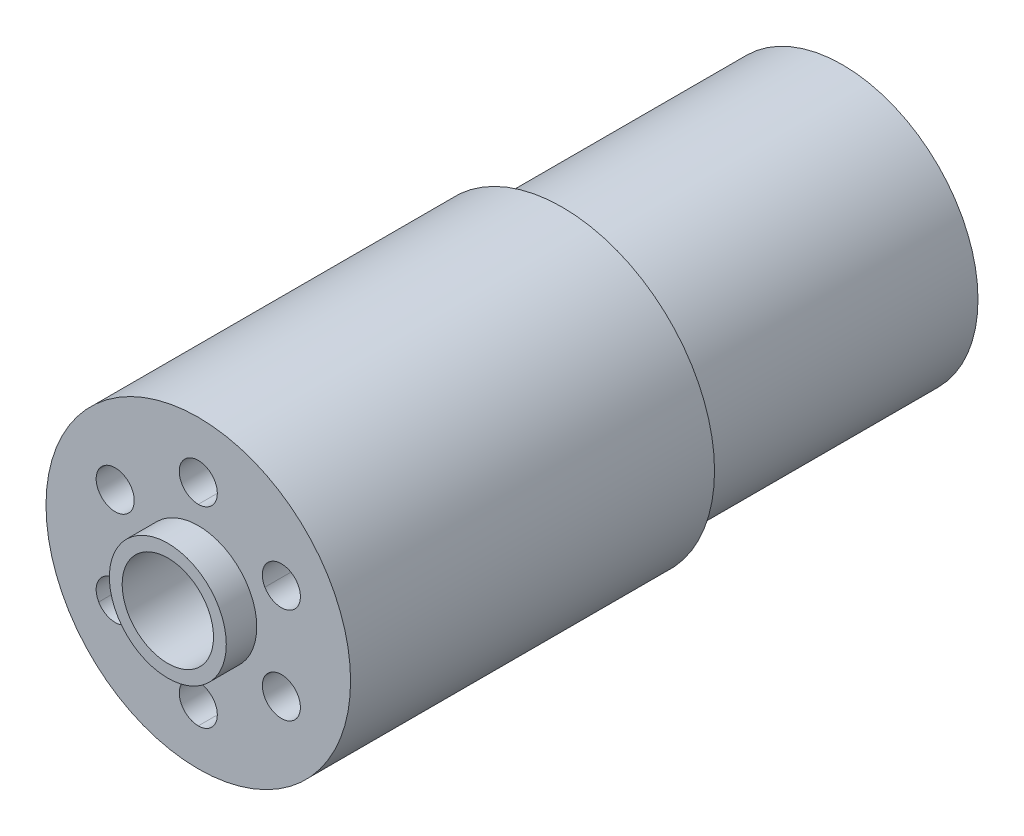
SolidWorks part; units mm, degrees
ref_plane "Front Plane" through (0, 0, 0) normal (0, 0, 1) x (1, 0, 0)
ref_plane "Top Plane" through (0, 0, 0) normal (0, 1, 0) x (1, 0, 0)
ref_plane "Right Plane" through (0, 0, 0) normal (1, 0, 0) x (0, 0, -1)
sketch "Sketch1" plane through (0, 0, 0) normal (0, 0, 1) x (1, 0, 0)
  circle A0 centre (0, 0) radius 25.4
  circle A8 centre (0, 0) radius 9.3953
  point P19 (0, 0)
  dimension "D1" = 50.8
  dimension "D2" = 16.0047
extrude "Boss-Extrude2" add sketch "Sketch1" along normal blind 107.442 contours A0
sketch "Sketch6" plane through (0, 0, 0) normal (0, 0, -1) x (-1, 0, 0)
  circle A0 centre (0, 0) radius 7.62
  circle A1 centre (-13.8581, 8.001) radius 3.175
  circle A2 centre (0, 16.002) radius 3.175
  circle A3 centre (13.8581, 8.001) radius 3.175
  circle A4 centre (13.8581, -8.001) radius 3.175
  circle A5 centre (0, -16.002) radius 3.175
  circle A6 centre (-13.8581, -8.001) radius 3.175
  point P18 (0, 0)
  dimension "D1" = 15.24
  dimension "D2" = 6.35
  dimension "D3" = 16.002
  dimension "D4" = 6
extrude "Cut-Extrude1" cut sketch "Sketch6" against normal blind 108.458
sketch "Sketch7" plane through (0, 0, 0) normal (0, 0, -1) x (-1, 0, 0)
  circle A0 centre (0, 0) radius 22.606
  circle A1 centre (0, 0) radius 25.4 construction
  circle A2 centre (0, 0) radius 25.4
  dimension "D1" = 2.794
extrude "Cut-Extrude2" cut sketch "Sketch7" against normal blind 46.736
sketch "Sketch8" plane through (0, 0, 107.442) normal (0, 0, 1) x (1, 0, 0)
  circle A0 centre (0, 0) radius 7.62
  circle A1 centre (0, 0) radius 9.75
  dimension "D1" = 19.5
  dimension "D2" = 15.24
extrude "Boss-Extrude7" add sketch "Sketch8" along normal blind 5.08
sketch "Sketch9" plane through (0, 0, 0) normal (0, 0, -1) x (-1, 0, 0)
  circle A0 centre (0, 0) radius 7.62
  circle A1 centre (0, 0) radius 9.75
  dimension "D1" = 19.5
  dimension "D2" = 15.24
extrude "Boss-Extrude8" add sketch "Sketch9" along normal blind 5.08
sketch "Sketch10" plane through (0, 0, 0) normal (0, 0, -1) x (-1, 0, 0)
  circle A0 centre (0, 16.002) radius 3.175 construction
  circle A1 centre (0, -16.002) radius 3.175 construction
  circle A2 centre (0, 0) radius 19.177 construction
  circle A3 centre (-13.8581, 8.001) radius 3.175 construction
  circle A4 centre (-13.8581, -8.001) radius 3.175 construction
  circle A5 centre (13.8581, -8.001) radius 3.175 construction
  circle A6 centre (0, 0) radius 12.827 construction
  point P0 (0, 19.177)
  point P1 (0, -19.177)
  point P9 (-16.6078, 9.5885)
  point P10 (-16.6078, -9.5885)
  point P13 (16.6078, -9.5885)
  point P16 (16.6078, 9.5885)
  point P20 (0, 12.827)
  point P21 (-10.9777, 6.6349)
  point P22 (-10.9777, -6.6349)
  point P23 (11.1085, -6.4135)
  point P24 (11.1085, 6.4135)
  point P25 (0, -12.827)
sketch "Sketch11" plane through (0, 0, 107.442) normal (0, 0, 1) x (1, 0, 0)
  point P0 (10.9777, 6.6349)
  point P2 (10.9777, -6.6349)
  point P4 (0, -12.827)
  point P6 (-11.1085, -6.4135)
  point P8 (-11.1085, 6.4135)
  point P10 (0, 12.827)
ref_plane "Plane1" through (0, 0, 0) normal (-1, 0, 0) x (0, 0, 1)
ref_plane "Plane3" through (0, 0, 0) normal (-0.5, -0.866, 0) x (-0.866, 0.5, 0)
ref_plane "Plane6" through (0, 0, 0) normal (0.5, -0.866, 0) x (-0.866, -0.5, 0)
split line "Split Line1"
split line "Split Line2"
split line "Split Line3"
ref_axis "Axis1" through (0, 0, 112.522) along (0, 0, -1)
